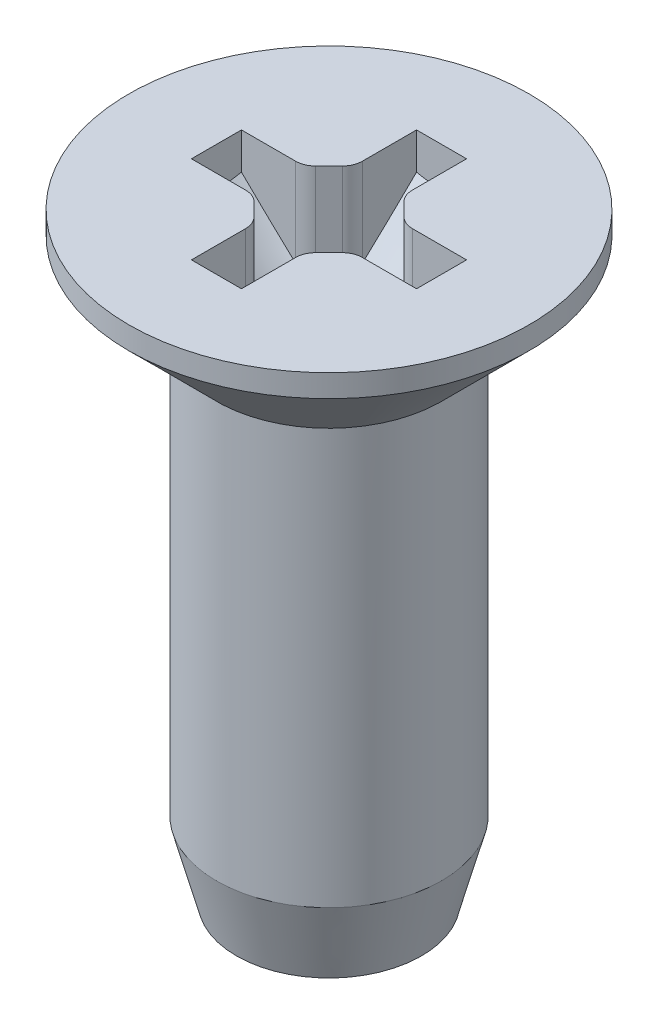
SolidWorks part; units mm, degrees
note: '?' marks a value the reader was unsure of.
ref_plane "Front" through (0, 0, 0) normal (0, 0, 1) x (1, 0, 0)
ref_plane "Top" through (0, 0, 0) normal (0, 1, 0) x (1, 0, 0)
ref_plane "Right" through (0, 0, 0) normal (1, 0, 0) x (0, 0, -1)
sketch "Sketch1" plane through (0, 0, 0) normal (0, 0, 1) x (1, 0, 0)
  line L0 (0, 0) -> (0, 33.993) construction
  line L1 (0, 0) -> (0, -12)
  line L2 (0, 0) -> (4, 0)
  line L3 (4, 0) -> (4, -0.45)
  line L4 (2.25, -2.2) -> (2.25, -12)
  line L5 (4, -0.45) -> (2.25, -2.2)
  line L6 (0, -12) -> (2.25, -12)
  dimension "D1" = 2.2
  dimension "D2" = 4.5
  dimension "D3" = 8
  dimension "D4" = 45
  dimension "D5" = 12
revolve "Revolve1" add sketch "Sketch1" angle 360 about L0
sketch "Sketch4" plane through (0, 0, 0) normal (1, 0, 0) x (0, 0, -1)
  line L0 (1.85, -12) -> (2.25, -10.5)
  line L1 (2.25, -10.5) -> (2.25, -12)
  line L2 (2.25, -12) -> (1.85, -12)
  line L3 (-2.25, -12) -> (2.25, -12) construction
  line L4 (2.25, -12) -> (2.25, -2.2) construction
  line L5 (0, 0) -> (0, -10.6254) construction
  dimension "D1" = 1.5
  dimension "D2" = 0.4
revolve "Cut-Revolve1" cut sketch "Sketch4" angle 360 about L5
ref_axis "Axis1" through (0, -2.2, 0) along (0, -1, 0)?
sketch "Sketch6" plane through (0, 0, 0) normal (0, 1, 0) x (1, 0, 0)
  line L0 (-0.5, 2.25) -> (0.5, 2.25)
  line L1 (0.5, 2.25) -> (0.5, 0.5)
  line L2 (0.5, 0.5) -> (2.25, 0.5)
  line L3 (2.25, 0.5) -> (2.25, -0.5)
  line L4 (2.25, -0.5) -> (0.5, -0.5)
  line L5 (0.5, -0.5) -> (0.5, -2.25)
  line L6 (0.5, -2.25) -> (-0.5, -2.25)
  line L7 (-0.5, -2.25) -> (-0.5, -0.5)
  line L8 (-0.5, -0.5) -> (-2.25, -0.5)
  line L9 (-2.25, -0.5) -> (-2.25, 0.5)
  line L10 (-2.25, 0.5) -> (-0.5, 0.5)
  line L11 (-0.5, 0.5) -> (-0.5, 2.25)
  line L12 (-0.5, 0.5) -> (0.5, -0.5) construction
  line L13 (0.5, 0.5) -> (-0.5, -0.5) construction
  dimension "D1" = 4.5
  dimension "D2" = 1
surface "Surface-Offset1" parameters "D1"=1
extrude "Cut-Extrude2" cut sketch "Sketch6" against normal up to surface (2.3287 mm away)
chamfer "Chamfer1" distance 0.5 angle 45 4 edges at (0.5, -1.1643, 0.5) (-0.5, -1.1643, 0.5) (0.5, -1.1643, -0.5) (-0.5, -1.1643, -0.5)
fillet "Fillet1" radius 0.4 8 edges at (-1, -0.9589, 0.5) (-0.5, -0.9589, 1) (0.5, -0.9589, 1) (1, -0.9589, 0.5) (1, -0.9589, -0.5) (0.5, -0.9589, -1) (-0.5, -0.9589, -1) (-1, -0.9589, -0.5)
